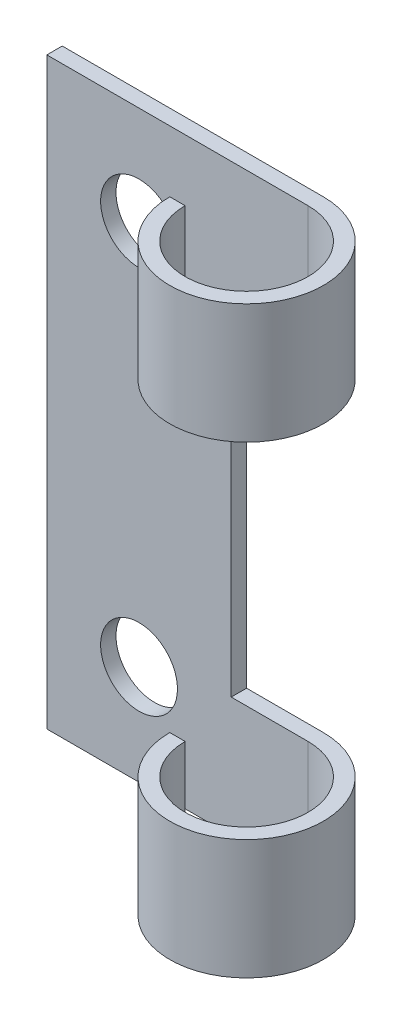
SolidWorks part; units mm, degrees
ref_plane "前视基准面" through (0, 0, 0) normal (0, 0, 1) x (1, 0, 0)
ref_plane "上视基准面" through (0, 0, 0) normal (0, 1, 0) x (1, 0, 0)
ref_plane "右视基准面" through (0, 0, 0) normal (1, 0, 0) x (0, 0, -1)
sketch "草图1" plane through (0, 0, 0) normal (0, 0, 1) x (1, 0, 0)
  line L1 (0, 0) -> (12, 0)
  line L2 (0, 0) -> (0, 38)
  line L3 (0, 38) -> (12, 38)
  line L4 (12, 0) -> (12, 38)
  circle A0 centre (6, 31.5) radius 2.5
  circle A1 centre (6, 6.5) radius 2.5
  dimension "D3" = 6
  dimension "D4" = 6.5
  dimension "D5" = 5
  dimension "D6" = 6
  dimension "D7" = 5
  dimension "D8" = 6.5
  dimension "D1" = 38
  dimension "D2" = 12
extrude "凸台-拉伸1" add sketch "草图1" along normal blind 1
sketch "草图2" plane through (0, 38, 0) normal (0, 1, 0) x (1, 0, 0)
  line L1 (12, 0) -> (0, 0) construction
  line L2 (12, 0) -> (17, 0)
  line L3 (12, -1) -> (12, 0) construction
  line L4 (12, 0) -> (12, -1)
  line L5 (12, -1) -> (17, -1)
  line L6 (12, -5) -> (13, -5)
  arc A0 (17, 0) -> (12, -5) centre (17, -5) cw
  arc A1 (17, -1) -> (13, -5) centre (17, -5) cw
  point P16 (0, 0)
  dimension "D1" = 5
extrude "凸台-拉伸2" add sketch "草图2" against normal blind 7.8
extrude "凸台-拉伸3" add sketch "草图2<2>" along normal blind 7.8 from surface starting at face at (6, 0, 0.5)
sketch "草图2<2>" plane through (0, 38, 0) normal (0, 1, 0) x (1, 0, 0) same geometry as "草图2"
